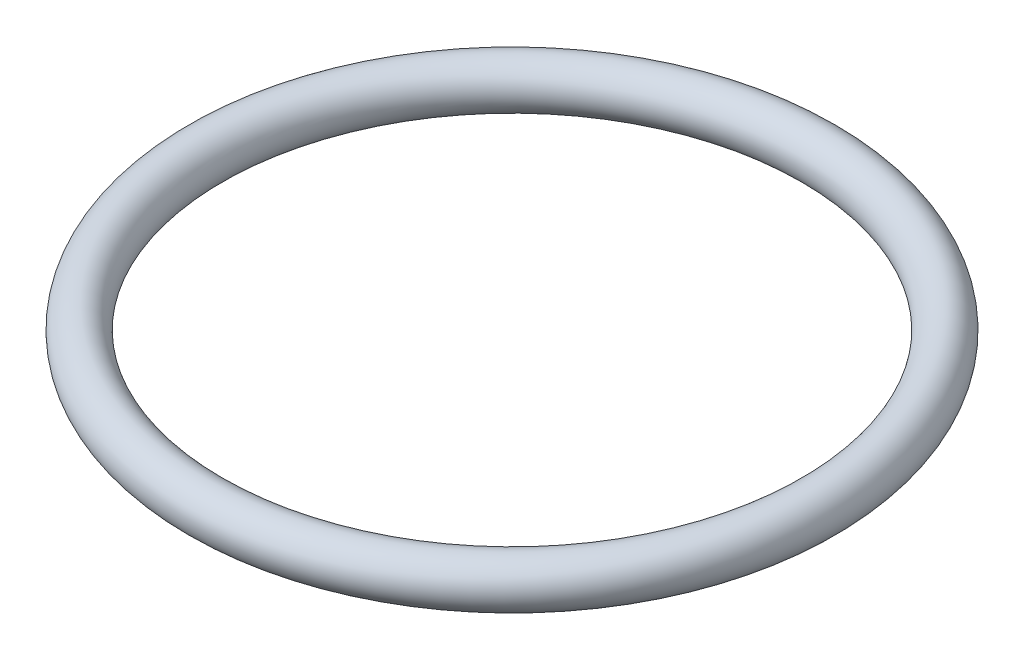
SolidWorks part; units mm, degrees
ref_plane "Front Plane" through (0, 0, 0) normal (0, 0, 1) x (1, 0, 0)
ref_plane "Top Plane" through (0, 0, 0) normal (0, 1, 0) x (1, 0, 0)
ref_plane "Right Plane" through (0, 0, 0) normal (1, 0, 0) x (0, 0, -1)
sketch "Sketch1" plane through (0, 0, 0) normal (0, 1, 0) x (1, 0, 0)
  circle A0 centre (0, 0) radius 28.25 construction
  circle A1 centre (0, 0) radius 24 construction
  circle A2 centre (0, 0) radius 26.125
  dimension "D1" = 56.5
  dimension "D2" = 48
  dimension "D3" = 52.25
sweep "Sweep1" add path "Sketch1" circular profile diameter 4 parameters "D3"=4
